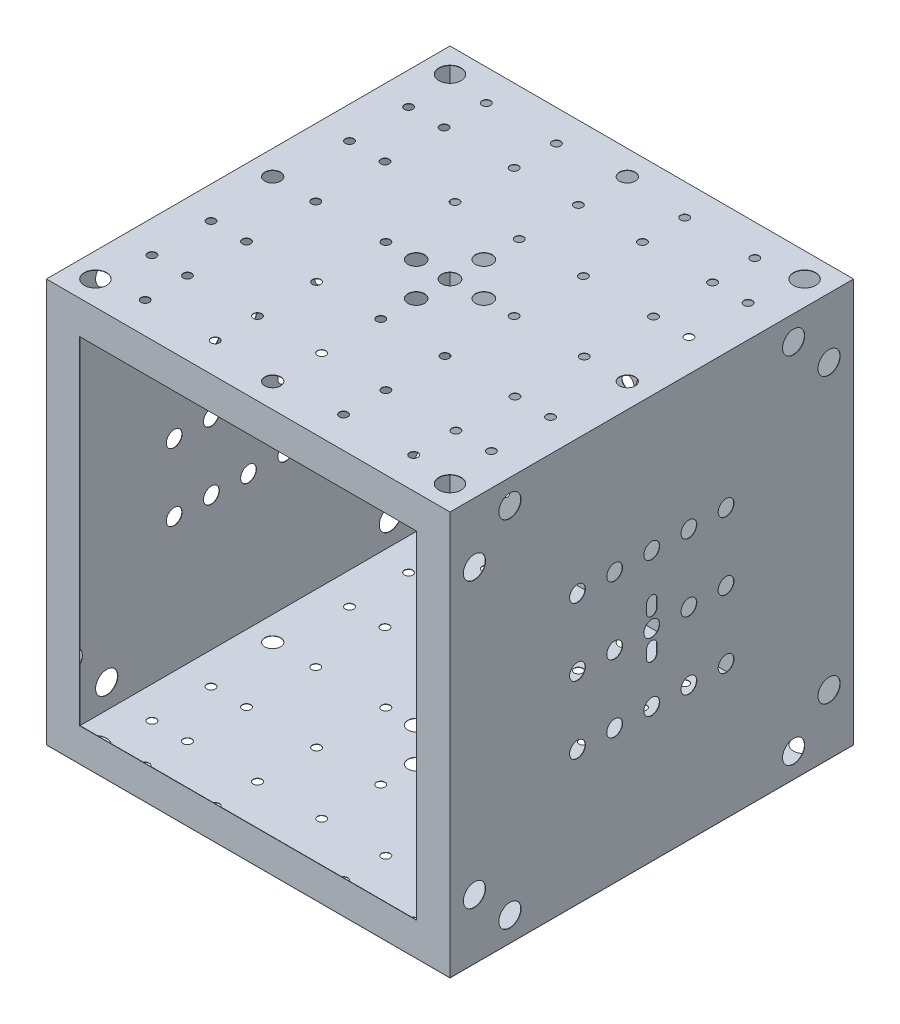
SolidWorks part; units mm, degrees
other "Markup1"
sketch "Sketch14" plane through (1195, 2390, 1195) normal (0.4693, 0.2273, 0.8533) x (0.8762, -0.2403, -0.4178)
ref_plane "Front" through (0, 0, 0) normal (0, 0, 1) x (1, 0, 0)
ref_plane "Top" through (0, 0, 0) normal (0, 1, 0) x (1, 0, 0)
ref_plane "Right" through (0, 0, 0) normal (1, 0, 0) x (0, 0, -1)
sketch "Sketch1" plane through (0, 0, 0) normal (0, 1, 0) x (1, 0, 0)
  line L1 (-1195, 1195) -> (1195, 1195)
  line L2 (-1195, 1195) -> (-1195, -1195)
  line L3 (-1195, -1195) -> (1195, -1195)
  line L4 (1195, 1195) -> (1195, -1195)
  line L5 (-1195, 1195) -> (1195, -1195) construction
  line L6 (-1195, -1195) -> (1195, 1195) construction
  point P0 (0, 0)
  dimension "D1" = 2390
  dimension "D2" = 2390
extrude "Boss-Extrude1" add sketch "Sketch1" along normal blind 2390
sketch "Sketch7" plane through (0, 0, 1195) normal (0, 0, 1) x (1, 0, 0)
  line L0 (-1195, 1195) -> (1195, 1195) construction
  line L1 (-1195, 2390) -> (-1195, 0) construction
  line L2 (1195, 2390) -> (1195, 0) construction
  line L3 (0, 2390) -> (0, 0) construction
  line L4 (-1195, 2390) -> (1195, 2390) construction
  line L5 (-1195, 0) -> (1195, 0) construction
  line L7 (-1193, 2388) -> (1193, 2388)
  line L8 (-1193, 2388) -> (-1193, 2)
  line L9 (-1193, 2) -> (1193, 2)
  line L10 (1193, 2388) -> (1193, 2)
  line L11 (-1193, 2388) -> (1193, 2) construction
  line L12 (-1193, 2) -> (1193, 2388) construction
  point P12 (0, 1195)
  dimension "D1" = 2
  dimension "D2" = 2
extrude "Cut-Extrude2" cut sketch "Sketch7" against normal blind 2388
sketch "Sketch10" plane through (0, 0, 1195) normal (0, 0, 1) x (1, 0, 0)
  line L0 (0, 0) -> (0, 2388) construction
  line L1 (1193, 2388) -> (-1193, 2388) construction
  line L2 (1195, 1195) -> (-1195, 1195) construction
  line L3 (1195, 2390) -> (1195, 0) construction
  line L4 (-1195, 2390) -> (-1195, 0) construction
  line L6 (-1195, 2388) -> (1195, 2388)
  line L7 (-1195, 2388) -> (-1195, 0)
  line L8 (-1195, 0) -> (1195, 0)
  line L9 (1195, 2388) -> (1195, 0)
  line L10 (-1195, 2388) -> (1195, 0) construction
  line L11 (-1195, 0) -> (1195, 2388) construction
  line L12 (-997.835, 2193) -> (997.835, 2193)
  line L13 (-997.835, 2193) -> (-997.835, 197)
  line L14 (-997.835, 197) -> (997.835, 197)
  line L15 (997.835, 2193) -> (997.835, 197)
  line L16 (-997.835, 2193) -> (997.835, 197) construction
  line L17 (-997.835, 197) -> (997.835, 2193) construction
  point P11 (0, 1194)
  point P17 (0, 1195)
  dimension "D1" = 195
extrude "Boss-Extrude4" add sketch "Sketch10" against normal blind 2
sketch "Sketch11" plane through (0, 2390, 0) normal (0, 1, 0) x (1, 0, 0)
  line L0 (0, -1195) -> (0, 1195) construction
  line L1 (-1195, -1195) -> (1195, -1195) construction
  line L2 (1195, 1195) -> (-1195, 1195) construction
  line L3 (-1195, 0) -> (1195, 0) construction
  line L4 (-1195, 1195) -> (-1195, -1195) construction
  line L5 (1195, -1195) -> (1195, 1195) construction
  line L6 (0, 0) -> (-1195, 1195) construction
  line L7 (0, 0) -> (200, 0) construction
  line L8 (0, 0) -> (0, 200) construction
  line L9 (-380, 0) -> (-380, 410) construction
  line L10 (-795, 410) -> (-795, 760) construction
  line L11 (-795, 760) -> (-795, 1010) construction
  circle A0 centre (0, 0) radius 49.85
  circle A1 centre (200, 0) radius 49.85
  circle A2 centre (-200, 0) radius 49.85
  circle A4 centre (0, 200) radius 49.85
  circle A5 centre (0, -200) radius 49.85
  circle A6 centre (-380, 0) radius 25
  circle A7 centre (-795, 0) radius 25
  circle A8 centre (-1050, 0) radius 46.75
  circle A9 centre (-1050, 1050) radius 65.8
  circle A10 centre (380, 0) radius 25
  circle A11 centre (795, 0) radius 25
  circle A12 centre (1050, 0) radius 46.75
  circle A13 centre (1050, 1050) radius 65.8
  circle A14 centre (-380, 410) radius 25
  circle A15 centre (-795, 410) radius 25
  circle A16 centre (380, 410) radius 25
  circle A17 centre (795, 410) radius 25
  circle A18 centre (0, 410) radius 25
  circle A19 centre (-795, 760) radius 25
  circle A20 centre (-380, 760) radius 25
  circle A21 centre (0, 760) radius 25
  circle A22 centre (380, 760) radius 25
  circle A23 centre (795, 760) radius 25
  circle A24 centre (-795, 1010) radius 25
  circle A25 centre (-380, 1010) radius 25
  circle A26 centre (380, 1010) radius 25
  circle A27 centre (795, 1010) radius 25
  circle A28 centre (0, 1050) radius 46.75
  circle A29 centre (-1005, 760) radius 25
  circle A30 centre (-1005, 410) radius 25
  circle A31 centre (1005, 410) radius 25
  circle A32 centre (1005, 760) radius 25
  circle A33 centre (1005, -410) radius 25
  circle A34 centre (795, -410) radius 25
  circle A35 centre (380, -410) radius 25
  circle A36 centre (0, -410) radius 25
  circle A37 centre (-380, -410) radius 25
  circle A38 centre (-795, -410) radius 25
  circle A39 centre (-1005, -410) radius 25
  circle A40 centre (-1005, -760) radius 25
  circle A41 centre (-795, -760) radius 25
  circle A42 centre (-380, -760) radius 25
  circle A43 centre (0, -760) radius 25
  circle A44 centre (380, -760) radius 25
  circle A45 centre (795, -760) radius 25
  circle A46 centre (1005, -760) radius 25
  circle A47 centre (1050, -1050) radius 65.8
  circle A48 centre (795, -1010) radius 25
  circle A49 centre (380, -1010) radius 25
  circle A50 centre (0, -1050) radius 46.75
  circle A51 centre (-380, -1010) radius 25
  circle A52 centre (-795, -1010) radius 25
  circle A53 centre (-1050, -1050) radius 65.8
  dimension "D1" = 99.7
  dimension "D7" = 50
  dimension "D8" = 50
  dimension "D10" = 93.5
  dimension "D12" = 131.6
  dimension "D16" = 50
  dimension "D22" = 93.5
  dimension "D24" = 50
  dimension "D27" = 50
  dimension "D3" = 200
  dimension "D5" = 200
  dimension "D6" = 380
  dimension "D9" = 795
  dimension "D11" = 1050
  dimension "D13" = 1050
  dimension "D14" = 2
  dimension "D15" = 410
  dimension "D17" = 410
  dimension "D19" = 350
  dimension "D21" = 250
  dimension "D23" = 1050
  dimension "D25" = 1005
  dimension "D26" = 760
  dimension "D28" = 350
  dimension "D29" = 210
  dimension "D2" = 2
  dimension "D4" = 2
  dimension "D18" = 2
  dimension "D20" = 2
extrude "Cut-Extrude3" cut sketch "Sketch11" against normal through all
sketch "Sketch12" plane through (0, 0, -1195) normal (0, 0, -1) x (-1, 0, 0)
  line L0 (-1195, 1195) -> (1195, 1195) construction
  line L1 (-1195, 2390) -> (-1195, 0) construction
  line L2 (1195, 2390) -> (1195, 0) construction
  line L3 (0, 2390) -> (0, 26.3654) construction
  line L4 (-1195, 2390) -> (1195, 2390) construction
  line L5 (0, 1195) -> (-1195, 2390) construction
  line L6 (0, 1195) -> (1195, 2390) construction
  circle A0 centre (0, 1195) radius 91.2
  circle A1 centre (0, 1335) radius 35.635
  circle A2 centre (-900, 2095) radius 65.8
  circle A3 centre (-222, 1577) radius 91.2
  circle A4 centre (222, 813) radius 91.2
  circle A5 centre (900, 2095) radius 65.8
  circle A6 centre (900, 295) radius 65.8
  circle A7 centre (-900, 295) radius 65.8
  circle A8 centre (-140, 1195) radius 35.635
  circle A9 centre (0, 1055) radius 35.635
  circle A10 centre (140, 1195) radius 35.635
  dimension "D1" = 182.4
  dimension "D2" = 71.27
  dimension "D4" = 131.6
  dimension "D6" = 182.4
  dimension "D11" = 182.4
  dimension "D3" = 140
  dimension "D5" = 900
  dimension "D7" = 222
  dimension "D8" = 382
  dimension "D9" = 222
  dimension "D10" = 382
extrude "Cut-Extrude4" cut sketch "Sketch12" against normal through all
sketch "Sketch13" plane through (-1195, 0, 0) normal (-1, 0, 0) x (0, 0, 1)
  line L0 (-1195, 1195) -> (1195, 1195) construction
  line L1 (0, 1055) -> (0, 1102.5) construction
  line L2 (30.9375, 1055) -> (30.9375, 1102.5)
  line L3 (-30.9375, 1055) -> (-30.9375, 1102.5)
  line L5 (0, 1335) -> (0, 1287.5) construction
  line L6 (30.9375, 1335) -> (30.9375, 1287.5)
  line L7 (-30.9375, 1335) -> (-30.9375, 1287.5)
  line L8 (0, 1195) -> (0, 1595) construction
  line L9 (0, 1595) -> (-220, 1595) construction
  line L10 (-1195, 2390) -> (1195, 0) construction
  line L12 (-1195, 2390) -> (-1195, 0) construction
  line L13 (1195, 2390) -> (1195, 0) construction
  line L15 (0, 2390) -> (0, 0) construction
  line L16 (-1195, 2390) -> (1195, 2390) construction
  circle A0 centre (0, 1195) radius 46.75
  arc A1 (30.9375, 1335) -> (-30.9375, 1335) centre (0, 1335) ccw
  arc A2 (-30.9375, 1287.5) -> (30.9375, 1287.5) centre (0, 1287.5) ccw
  circle A3 centre (0, 1595) radius 46.75
  circle A4 centre (-220, 1595) radius 46.75
  circle A5 centre (-220, 1195) radius 46.75
  circle A6 centre (-440, 1595) radius 46.75
  circle A7 centre (-440, 1195) radius 46.75
  circle A8 centre (-840, 2245) radius 65.8
  circle A9 centre (-1050, 2035) radius 65.8
  circle A10 centre (220, 1595) radius 46.75
  circle A11 centre (220, 1195) radius 46.75
  circle A12 centre (440, 1195) radius 46.75
  circle A13 centre (440, 1595) radius 46.75
  circle A14 centre (840, 2245) radius 65.8
  circle A15 centre (1050, 2035) radius 65.8
  circle A16 centre (-440, 795) radius 46.75
  circle A17 centre (-220, 795) radius 46.75
  circle A18 centre (0, 795) radius 46.75
  circle A19 centre (220, 795) radius 46.75
  circle A20 centre (440, 795) radius 46.75
  circle A21 centre (1050, 355) radius 65.8
  circle A22 centre (840, 145) radius 65.8
  circle A23 centre (-840, 145) radius 65.8
  circle A24 centre (-1050, 355) radius 65.8
  arc A25 (30.9375, 1055) -> (-30.9375, 1055) centre (0, 1055) cw
  arc A26 (-30.9375, 1102.5) -> (30.9375, 1102.5) centre (0, 1102.5) cw
  point P15 (0, 1311.25)
  point P73 (0, 1078.75)
  dimension "D1" = 93.5
  dimension "D3" = 30.9375
  dimension "D9" = 131.6
  dimension "D13" = 1195
  dimension "D2" = 92.5
  dimension "D4" = 47.5
  dimension "D6" = 400
  dimension "D8" = 220
  dimension "D10" = 1050
  dimension "D11" = 840
  dimension "D12" = 0
  dimension "D14" = 1195
  dimension "D15" = 116.25
  dimension "D5" = 2
  dimension "D7" = 3
extrude "Cut-Extrude5" cut sketch "Sketch13" against normal through all
split "Split1" bodies to split 111 resulting bodies 112 113 split by face at (0, 2, 150.15)
